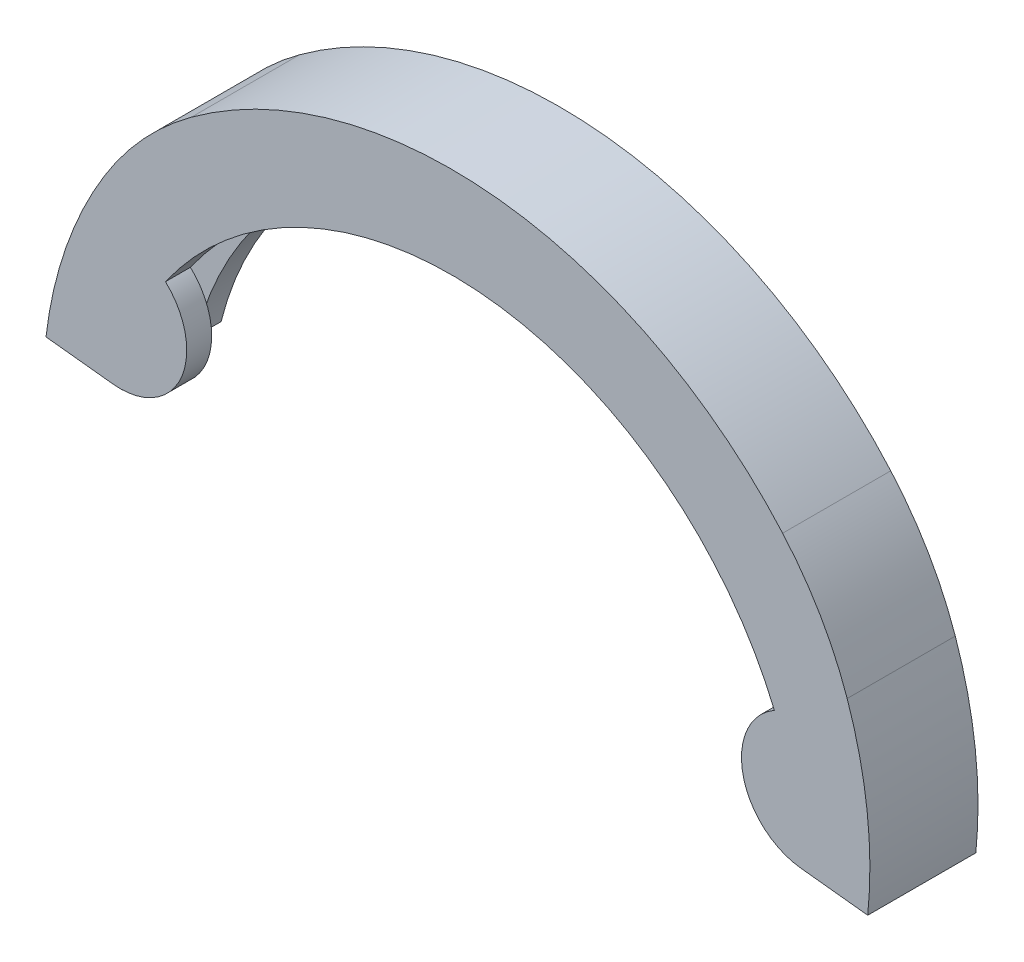
SolidWorks part; units mm, degrees
ref_plane "Front Plane" through (0, 0, 0) normal (0, 0, 1) x (1, 0, 0)
ref_plane "Top Plane" through (0, 0, 0) normal (0, 1, 0) x (1, 0, 0)
ref_plane "Right Plane" through (0, 0, 0) normal (1, 0, 0) x (0, 0, -1)
sketch "Sketch1" plane through (0, 0, 0) normal (0, 1, 0) x (1, 0, 0)
  line L1 (0, 0) -> (50, 0)
  line L2 (0, 0) -> (0, 7)
  line L3 (0, 7) -> (50, 7)
  line L4 (50, 0) -> (50, 7)
revolve "Revolve5" add sketch "Sketch1" angle 167.5 about L2 reverse direction yes
sketch "Sketch8" plane through (0, 0, 0) normal (0, 0, 1) x (1, 0, 0)
  line L0 (-48.8148, 10.822) -> (50, 0) construction
sketch "Sketch9" plane through (0, 0, -7) normal (0, 0, -1) x (-1, 0, 0)
  line L0 (-50, 0) -> (48.8148, 10.822) construction
shell "Shell2" thickness 3 removed face at (-24.4074, 5.411, -3.5) removed face at (25, 0, -3.5) outward yes
sketch "Sketch11" plane through (0, 0, 3) normal (0, 0, 1) x (1, 0, 0)
  line L0 (-51.7437, 11.4713) -> (53, 0)
extrude "Cut-Extrude3" cut sketch "Sketch11" against normal blind 10 and the other way through all flip side to cut contours L0
sketch "Sketch12" plane through (0, 0, -10) normal (0, 0, -1) x (-1, 0, 0)
  line L0 (-53, 0) -> (51.7437, 11.4713)
extrude "Cut-Extrude4" cut sketch "Sketch12" against normal blind 10 and the other way through all flip side to cut contours L0
sketch "Sketch13" plane through (0, 0, -10) normal (0, 0, -1) x (-1, 0, 0)
  line L0 (-50, 0) -> (48.8148, 10.822) construction
  line L1 (-50, 0) -> (-55.7837, 52.8108) construction
  line L2 (48.8148, 10.822) -> (43.0311, 63.6327) construction
  line L3 (-55.7837, 52.8108) -> (43.0311, 63.6327) construction
  line L4 (48.7792, 11.1466) -> (47.4197, 23.5606)
  line L6 (-50.0356, 0.3247) -> (-51.3951, 12.7389)
extrude "Cut-Extrude-Thin1" cut sketch "Sketch13" against normal blind 20 and the other way through all flip side to cut thin contours L4 thin type one direction wall 10
sketch "Sketch14" plane through (0, 0, -10) normal (0, 0, -1) x (-1, 0, 0)
  line L4 (-50.0356, 0.3247) -> (-51.3941, 12.7294)
  line L5 (48.7792, 11.1466) -> (-53, 0) construction
extrude "Cut-Extrude-Thin2" cut sketch "Sketch14" against normal blind 20 and the other way through all thin contours L4 thin type one direction reverse wall 30
sketch "Sketch15" plane through (0, 0, -10) normal (0, 0, -1) x (-1, 0, 0)
  line L0 (48.7792, 11.1466) -> (47.4197, 23.5606) construction
  line L1 (48.7792, 11.1466) -> (-50.0356, 0.3247) construction
  arc A0 (-50.0356, 0.3247) -> (48.7792, 11.1466) centre (0, 0) cw construction
  arc A1 (-41.9827, 1.2066) -> (40.7264, 10.2647) centre (0, 0) cw
extrude "Cut-Extrude-Thin3" cut sketch "Sketch15" against normal blind 20 and the other way through all thin contours A1 thin type one direction wall 30
sketch "Sketch18" plane through (0, 0, 3) normal (0, 0, 1) x (1, 0, 0)
  line L0 (-40.7264, 10.2647) -> (41.9827, 1.2066) construction
  line L1 (-40.7264, 10.2647) -> (-39.8554, 18.2172) construction
  line L2 (41.9827, 1.2066) -> (42.8536, 9.159) construction
  line L3 (-39.8554, 18.2172) -> (42.8536, 9.159) construction
  circle A4 centre (-39.8554, 18.2172) radius 8
  circle A6 centre (42.8536, 9.159) radius 8
extrude "Boss-Extrude3" add sketch "Sketch18" against normal blind 3 contours A6 | A4
sketch "Sketch21" plane through (0, 0, 3) normal (0, 0, 1) x (1, 0, 0)
  line L0 (-40.7264, 10.2647) -> (41.9827, 1.2066) construction
  line L1 (-40.7264, 10.2647) -> (-39.8641, 18.1381) construction
  line L2 (41.9827, 1.2066) -> (42.8449, 9.08) construction
  line L3 (-39.8641, 18.1381) -> (42.8449, 9.08) construction
  circle A0 centre (-40, 18.2) radius 8 construction
  circle A1 centre (42.8449, 9.08) radius 8.0795 construction
sketch "Sketch26" plane through (0, 0, 3) normal (0, 0, 1) x (1, 0, 0)
  line L0 (-48.8148, 10.822) -> (50, 0) construction
  arc A0 (-48.7792, 11.1466) -> (-36.8855, 38.0587) centre (0.5926, 5.411) cw
  arc A1 (51.4502, 12.7233) -> (-47.4724, 23.5663) centre (0, 0) ccw construction
extrude "Cut-Extrude-Thin11" cut sketch "Sketch26" against normal blind 20 and the other way through all thin contours A0 thin type one direction reverse wall 20
sketch "Sketch27" plane through (0, 0, 3) normal (0, 0, 1) x (1, 0, 0)
  line L0 (-48.8148, 10.822) -> (50, 0) construction
  arc A0 (50.0356, 0.3247) -> (44.2486, 29.173) centre (0.5926, 5.411) ccw
  arc A1 (51.4502, 12.7233) -> (-36.8855, 38.0587) centre (0, 0) ccw construction
extrude "Cut-Extrude-Thin12" cut sketch "Sketch27" against normal blind 20 and the other way through all flip side to cut thin contours A0 thin type one direction wall 20
fillet "Fillet2" radius 40 2 edges at (44.2486, 29.173, -3.5) (-36.8855, 38.0587, -3.5)
